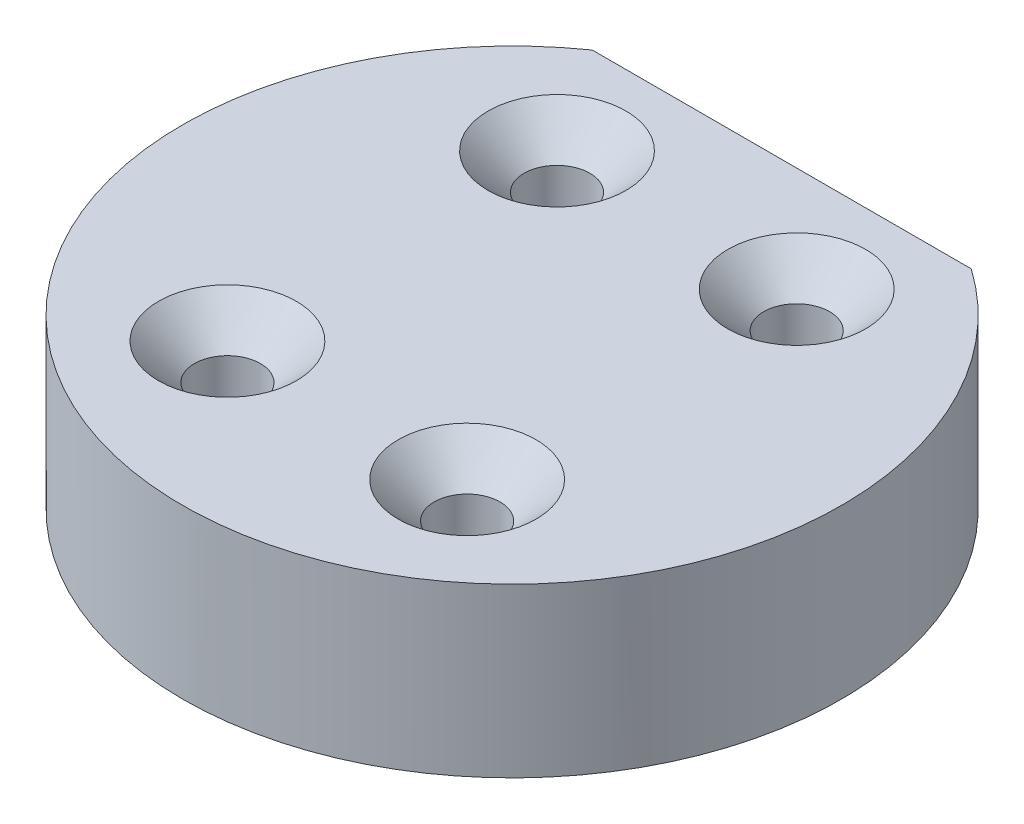
SolidWorks part; units mm, degrees
ref_plane "Front Plane" through (0, 0, 0) normal (0, 0, 1) x (1, 0, 0)
ref_plane "Top Plane" through (0, 0, 0) normal (0, 1, 0) x (1, 0, 0)
ref_plane "Right Plane" through (0, 0, 0) normal (1, 0, 0) x (0, 0, -1)
sketch "Sketch1" plane through (0, 0, 0) normal (0, 1, 0) x (1, 0, 0)
  line L0 (0, 0) -> (0, 68.5524) construction
  line L1 (0, 52.4907) -> (0, -49.3242) construction
  line L2 (10, -13.75) -> (10, 13.75)
  line L3 (10, -13.75) -> (-10, -13.75)
  line L4 (10, 13.75) -> (-10, 13.75)
  line L5 (-10, -13.75) -> (-10, 13.75)
  line L6 (10, -13.75) -> (-10, 13.75) construction
  line L7 (10, 13.75) -> (-10, -13.75) construction
  circle A0 centre (0, 0) radius 27.5
  circle A1 centre (-10, 13.75) radius 2.75
  circle A2 centre (10, 13.75) radius 2.75
  circle A3 centre (10, -13.75) radius 2.75
  circle A4 centre (-10, -13.75) radius 2.75
  dimension "D1" = 55
  dimension "D5" = 5.5
  dimension "D3" = 27.5
  dimension "D4" = 20
extrude "Boss-Extrude1" add sketch "Sketch1" along normal blind 14 contours A0 A4 L5 A1 L4 A2 L2 A3 L3 | A4 L3 A3 L2 A2 L4 A1 L5 region at (0, 0, 0) region at (-26.7222, 0, 0)
chamfer "Chamfer1" distance 3 angle 45 4 edges at (-10, 14, 16.5) (10, 14, 16.5) (10, 14, -11) (-10, 14, -11)
sketch "Sketch2" plane through (0, 14, 0) normal (0, -1, 0) x (1, 0, 0)
  line L0 (0, 15.5283) -> (0, -9.3063) construction
  line L1 (-27.5, -22.5) -> (-27.5, 0) construction
  line L2 (-27.5, -22.5) -> (27.5, -22.5)
  line L3 (-27.5, -22.5) -> (-27.5, -27.5)
  line L4 (-27.5, -27.5) -> (27.5, -27.5)
  line L5 (27.5, -22.5) -> (27.5, -27.5)
  line L6 (-27.5, -22.5) -> (27.5, -27.5) construction
  line L7 (-27.5, -27.5) -> (27.5, -22.5) construction
  line L8 (-27.5, 0) -> (27.5, 0) construction
  circle A0 centre (0, 0) radius 27.5 construction
  circle A1 centre (0, 0) radius 27.5 construction
  point P1 (0, -25)
  dimension "D1" = 5
extrude "Cut-Extrude1" cut sketch "Sketch2" along normal blind 7
equation "\"LOGO_SIZE\"= 40"
equation "\"SECTION_SIZE\"= \"LOGO_SIZE\" / 6"
